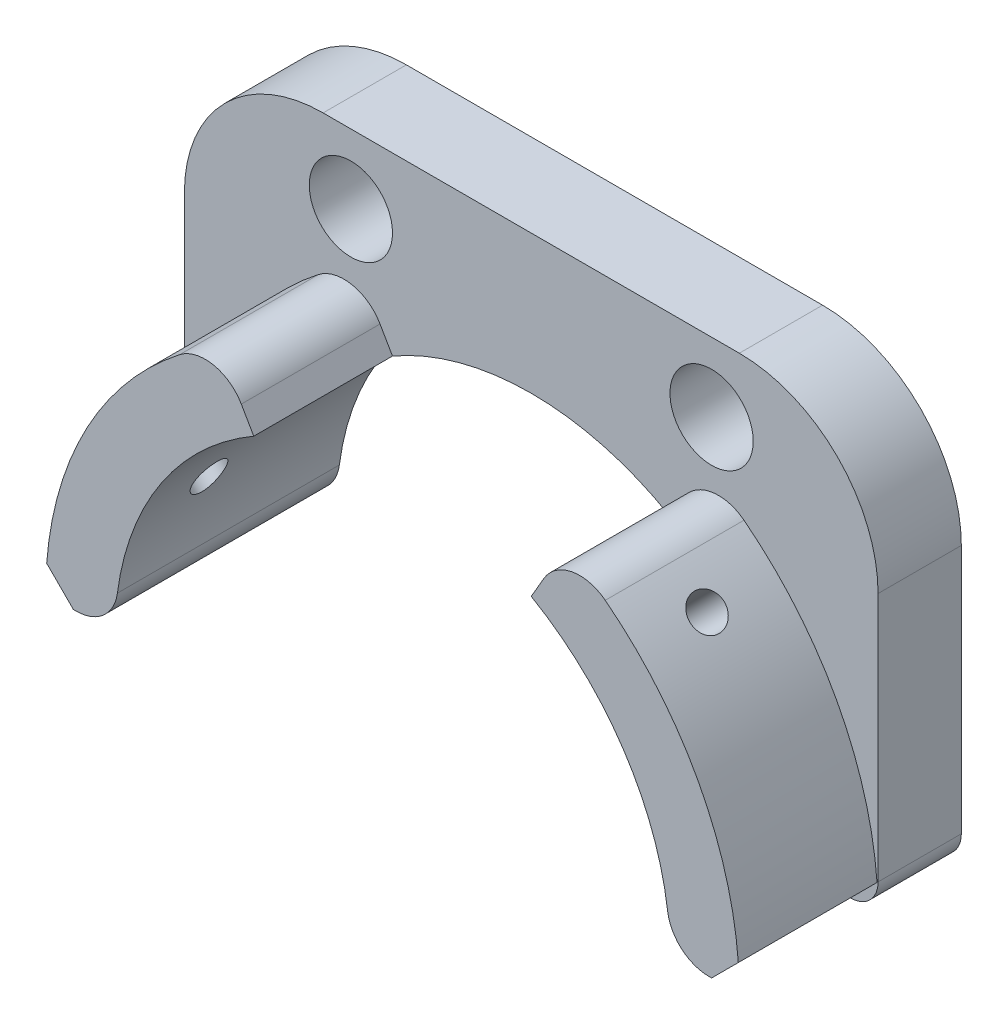
SolidWorks part; units mm, degrees
ref_plane "Płaszczyzna przednia" through (0, 0, 0) normal (0, 0, 1) x (1, 0, 0)
ref_plane "Płaszczyzna górna" through (0, 0, 0) normal (0, 1, 0) x (1, 0, 0)
ref_plane "Płaszczyzna prawa" through (0, 0, 0) normal (1, 0, 0) x (0, 0, -1)
sketch "Sketch1" plane through (0, 0, 0) normal (0, 0, 1) x (1, 0, 0)
  line L0 (25, 0) -> (-25, 0)
  circle A0 centre (0, 0) radius 20
  circle A1 centre (0, 0) radius 25
  dimension "D1" = 40
  dimension "D2" = 50
extrude "Boss-Extrude1" add sketch "Sketch1" along normal blind 6 contours L0 A1 A0
sketch "Sketch2" plane through (0, 0, 6) normal (0, 0, 1) x (1, 0, 0)
  line L0 (0, 0) -> (0, 9.8422) construction
  line L1 (0, 0) -> (-12.5, 21.6506)
  line L2 (20, 0) -> (25, 0)
  line L3 (-25, 0) -> (-20, 0)
  line L4 (20, 0) -> (25, 0)
  line L5 (-25, 0) -> (-20, 0)
  line L6 (0, 0) -> (12.5, 21.6506)
  arc A2 (25, 0) -> (-25, 0) centre (0, 0) ccw
  arc A3 (20, 0) -> (-20, 0) centre (0, 0) ccw
  arc A4 (25, 0) -> (-25, 0) centre (0, 0) ccw
  arc A5 (20, 0) -> (-20, 0) centre (0, 0) ccw
  line M7 (20, 0) -> (25, 0)
  arc M8 (25, 0) -> (-25, 0) centre (0, 0) ccw
  line M9 (-25, 0) -> (-20, 0)
  arc M10 (-20, 0) -> (20, 0) centre (0, 0) cw
  dimension "D2" = 60
  dimension "D1" = 0
extrude "Boss-Extrude2" add sketch "Sketch2" along normal blind 10 contours L1 M10 M8 M9 | L6 M10 M7 M8
sketch "Sketch3" plane through (0, 0, 0) normal (0, 0, -1) x (-1, 0, 0)
  line L0 (-25, 0) -> (-25, 30)
  line L1 (-25, 30) -> (25, 30)
  line L2 (25, 30) -> (25, 0)
  arc A0 (25, 0) -> (-25, 0) centre (0, 0) ccw construction
  arc A1 (25, 0) -> (-25, 0) centre (0, 0) ccw
  dimension "D1" = 30
extrude "Boss-Extrude3" add sketch "Sketch3" against normal up to surface (6 mm away) up to face at (0, 20.9928, 6)
sketch "Sketch4" plane through (0, 0, 6) normal (0, 0, 1) x (1, 0, 0)
  circle A0 centre (13, 25) radius 3 construction
  circle A1 centre (-13, 25) radius 3 construction
  circle A2 centre (13, 25) radius 3
  circle A3 centre (-13, 25) radius 3
extrude "Cut-Extrude1" cut sketch "Sketch4" against normal through all
ref_plane "Plane1" through (-17.6777, 17.6777, 0) normal (-0.7071, 0.7071, 0) x (0, 0, -1)
sketch "Sketch6" plane through (0, 0, 16) normal (0, 0, 1) x (1, 0, 0)
  line L0 (0, 0) -> (-24.8084, 24.8084)
  line L1 (0, 0) -> (0, 12.4042) construction
  line L2 (0, 0) -> (24.8084, 24.8084)
  dimension "D1" = 45
hole_wizard "Tap Drill for M3 Tap1" positions "Sketch9" profile "Sketch10" hole size "M3" standard "DIN" end condition through all
sketch "Sketch9" plane through (-17.6777, 17.6777, 0) normal (-0.7071, 0.7071, 0) x (0, 0, -1)
  line L0 (-11, 7.0711) -> (-6, 7.0711)
  line L1 (-6, 17.6777) -> (-6, -3.5355) construction
  line L3 (-6, 17.6777) -> (-6, -6.4705) construction
  point P1 (-11, 7.0711)
  dimension "D1" = 5
sketch "Sketch10" plane through (-22.6777, 12.6777, 11) normal (0, 0, 1) x (-0.7071, -0.7071, 0)
  line L0 (0, 0) -> (0, 42.6777)
  line L1 (0, 42.6777) -> (1.25, 42.6777)
  line L2 (1.25, 42.6777) -> (1.25, 0)
  line L5 (1.25, 0) -> (0, 0)
  line L11 (0, -6.35) -> (0, 107.95) construction
  dimension "Thru Hole Dia." = 2.5
  dimension "Thru Hole Depth" = 42.6777
ref_plane "Plane2" through (17.6777, 17.6777, 0) normal (0.7071, 0.7071, 0) x (0, 0, -1)
hole_wizard "Tap Drill for M3 Tap2" positions "Sketch11" profile "Sketch12" hole size "M3" standard "DIN" end condition through all
sketch "Sketch11" plane through (17.6777, 17.6777, 0) normal (0.7071, 0.7071, 0) x (0, 0, -1)
  line L0 (-6, 6.4705) -> (-6, -17.6777) construction
  point P0 (-11, 0)
  dimension "D1" = 5
sketch "Sketch12" plane through (17.6777, 17.6777, 11) normal (0, 0, 1) x (-0.7071, 0.7071, 0)
  line L0 (0, 0) -> (0, 42.6777)
  line L1 (0, 42.6777) -> (1.25, 42.6777)
  line L2 (1.25, 42.6777) -> (1.25, 0)
  line L5 (1.25, 0) -> (0, 0)
  line L11 (0, -6.35) -> (0, 107.95) construction
  dimension "Thru Hole Dia." = 2.5
  dimension "Thru Hole Depth" = 42.6777
chamfer "Chamfer1" distance 2 angle 45 1 edges at (25, 0, 11)
fillet "Fillet1" radius 3 4 edges at (-12.5, 21.6506, 11) (12.5, 21.6506, 11) (20, 0, 8) (-20, 0, 8)
fillet "Fillet2" radius 10 2 edges at (25, 30, 3) (-25, 30, 3)
fillet "Fillet3" radius 2 4 edges at (25, 0, 3) (-25, 0, 3) (24, 0, 6) (-24, 0, 6)
